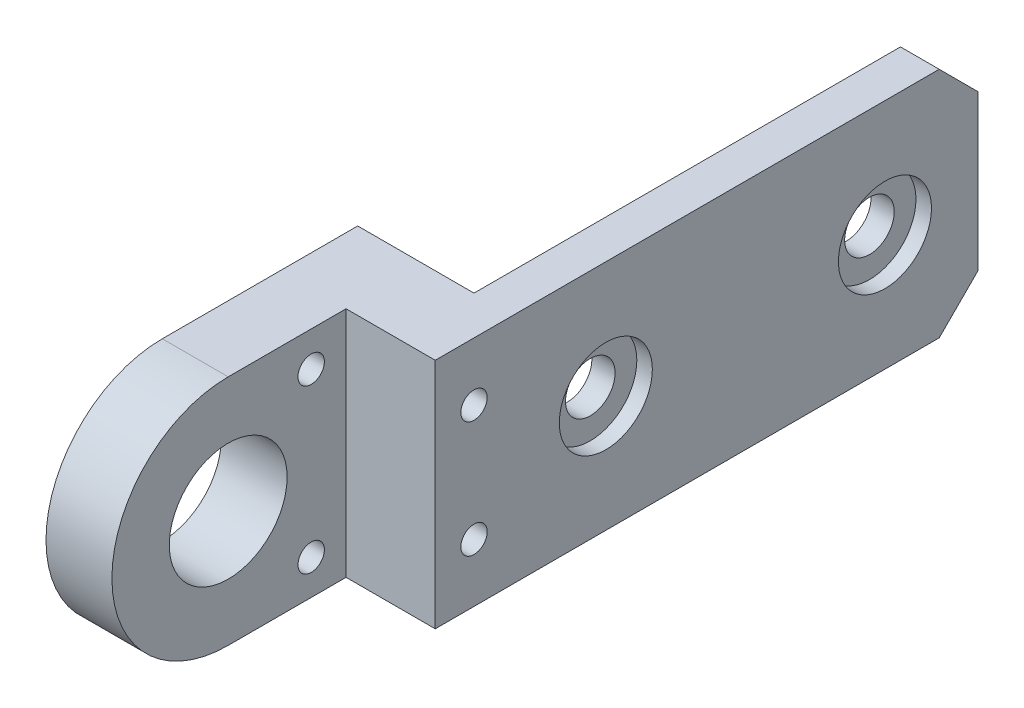
SolidWorks part; units mm, degrees
ref_plane "Front Plane" through (0, 0, 0) normal (1, 0, 0) x (0, 1, 0)
ref_plane "Top Plane" through (0, 0, 0) normal (0, 0, 1) x (0, 1, 0)
ref_plane "Right Plane" through (0, 0, 0) normal (0, 1, 0) x (-1, 0, 0)
sketch "Sketch1" plane through (0, 0, 0) normal (1, 0, 0) x (0, 1, 0)
  line L0 (-15, 0) -> (-15, -85.2)
  line L1 (-15, -85.2) -> (15, -85.2)
  line L2 (15, -85.2) -> (15, 0)
  line L3 (-15, -25.2) -> (15, -25.2)
  line L4 (-15, -80.2) -> (-10, -85.2)
  line L5 (10, -85.2) -> (15, -80.2)
  line L6 (-15, -15.2) -> (15, -15.2)
  circle A0 centre (0, 0) radius 7.6
  circle A1 centre (0, 0) radius 15
  circle A2 centre (0, -37.2) radius 3.2
  circle A3 centre (0, -37.2) radius 6
  circle A4 centre (0, -73.2) radius 3.2
  circle A5 centre (0, -73.2) radius 6
  circle A6 centre (-7.5, -20.2) radius 1.4
  circle A7 centre (7.5, -20.2) radius 1.7
  circle A8 centre (7.5, -20.2) radius 1.4
  circle A9 centre (-7.5, -20.2) radius 1.7
  circle A10 centre (-10.5, -10.7) radius 1.7
  circle A11 centre (-10.5, -10.7) radius 3
  circle A12 centre (-10.5, -10.7) radius 1.4
  circle A13 centre (10.5, -10.7) radius 1.4
  circle A14 centre (10.5, -10.7) radius 1.7
  circle A15 centre (10.5, -10.7) radius 3
  dimension "D1" = 30
  dimension "D2" = 15.2
  dimension "D5" = 6.4
  dimension "D6" = 12
  dimension "D13" = 3.4
  dimension "D14" = 2.8
  dimension "D18" = 6
  dimension "D4" = 60
  dimension "D7" = 12
  dimension "D9" = 5
  dimension "D10" = 5
  dimension "D11" = 5
  dimension "D3" = 15.2
  dimension "D12" = 10
  dimension "D8" = 12
  dimension "D15" = 5
  dimension "D16" = 7.5
  dimension "D17" = 7.5
  dimension "D19" = 4.5
  dimension "D20" = 4.5
  dimension "D21" = 14.9913
  dimension "D22" = 4.5
  dimension "D23" = 4.5
extrude "Boss-Extrude1" add sketch "Sketch1" along normal blind 8.5 contours A1 A0 | A1 L0 L6 L2 | L6 L0 L3 L2 A9 A7 | A1 A11 A10 | A1 A15 A14 | A1 A15 A14 | A1 A11 A10 region at (0, -14.6639, -4.4914) region at (0, 0, 14.5757) region at (0, 0, -20.2) region at (0, -9.2606, -8.0443) region at (0, -12.1104, -8.9777) region at (0, 13.1504, -9.4631) region at (0, 11.9943, -8.8916)
extrude "Boss-Extrude2" add sketch "Sketch1<4>" along normal blind 15 contours L6 L0 L3 L2 A9 A7 region at (0, 0, -20.2)
sketch "Sketch1<4>" plane through (0, 0, 0) normal (1, 0, 0) x (0, 1, 0) same geometry as "Sketch1"
extrude "Boss-Extrude3" add sketch "Sketch1<5>" along normal blind 3 from surface contours L1 L5 L2 L3 L0 L4 A5 A3 | L6 L0 L3 L2 A9 A7 | A3 A2 | A5 A4 region at (0, 0, -20.2) region at (0, 0, -54.7427) region at (0, -5.8303, -37.2) region at (0, -5.8303, -73.2) starting at face at (15, -7.5, -21.9)
sketch "Sketch1<5>" plane through (0, 0, 0) normal (1, 0, 0) x (0, 1, 0) same geometry as "Sketch1"
extrude "Boss-Extrude4" add sketch "Sketch1<6>" along normal blind 2 from surface contours L1 L5 L2 L3 L0 L4 A5 A3 | L6 L0 L3 L2 A9 A7 region at (0, 0, -20.2) region at (0, 0, -54.7427) starting at face at (18, 7.5, -21.9)
sketch "Sketch1<6>" plane through (0, 0, 0) normal (1, 0, 0) x (0, 1, 0) same geometry as "Sketch1"
equation "\"D7@Sketch1\"=\"D4@Sketch1\"/5"
equation "\"D11@Sketch1\"=\"D10@Sketch1\""
equation "\"D8@Sketch1\"=\"D7@Sketch1\""
equation "\"D15@Sketch1\"=\"D12@Sketch1\"/2"
equation "\"D16@Sketch1\"=\"D1@Sketch1\"/4"
equation "\"D17@Sketch1\"=\"D16@Sketch1\""
equation "\"D20@Sketch1\"=\"D19@Sketch1\""
equation "\"D22@Sketch1\"=\"D20@Sketch1\""
equation "\"D23@Sketch1\"=\"D19@Sketch1\""
